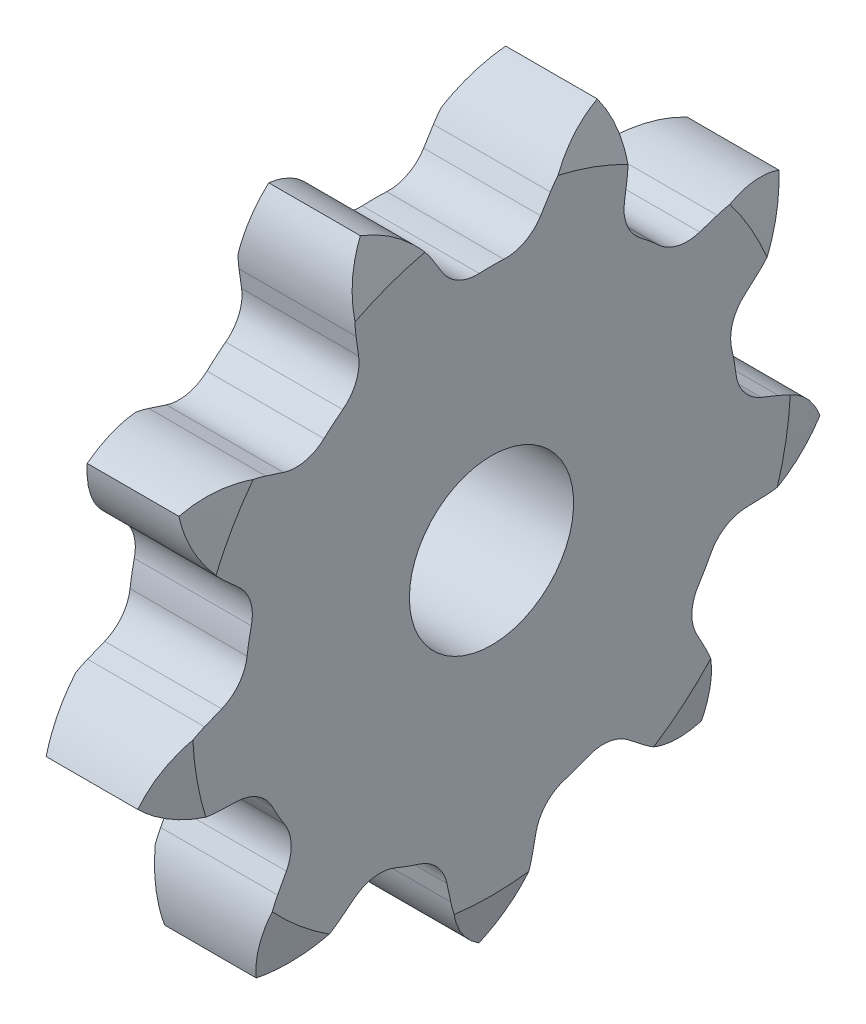
SolidWorks part; units mm, degrees
ref_plane "Plane1" through (0, 0, 0) normal (0, 0, 1) x (1, 0, 0)
ref_plane "Plane2" through (0, 0, 0) normal (0, 1, 0) x (1, 0, 0)
ref_plane "Plane3" through (0, 0, 0) normal (1, 0, 0) x (0, 0, -1)
sketch "Clipboard" plane through (0, 0, 0) normal (0, 1, 0) x (1, 0, 0)
  line L0 (0, 0) -> (62.7182, -9.9336)
  line L1 (-15, 0) -> (100, 0) construction
  line L2 (0, 0) -> (-2.1039, 2.3779)
  line L3 (0, 0) -> (-11.863, 4.5341)
  line L4 (0, 0) -> (8.5297, 1.351)
  line L5 (0, 0) -> (-71.3958, -26.6285)
  line L6 (0, 0) -> (-30.0043, -20.244)
  line L7 (-2.1039, 2.3779) -> (14.2981, 76.7917)
  line L8 (-76.2, 54.61) -> (-19.7358, 54.61)
  line L9 (-66.6514, 23.5599) -> (-51.1233, 26.8605)
  line L10 (-76.2, 71.12) -> (16.6308, 71.12)
  line L11 (0, 0) -> (-38.1, 0)
  line L12 (-76.2, 101.6) -> (-31.75, 101.6)
  circle A0 centre (0, 0) radius 15.875
  circle A1 centre (0, 0) radius 25.4
  circle A2 centre (0, 0) radius 25.4
  dimension "Num_teeth" = 9
  dimension "Pitch_radius" = 92.8308
  dimension "Width" = 38.1
  dimension "F" = 44.45
  dimension "H" = 15.875
  dimension "Thickness" = 36.195
sketch "BasProSke" plane through (0, 0, 0) normal (0, 1, 0) x (1, 0, 0)
  line L0 (-10, 0) -> (60, 0) construction
  line L1 (0, 0) -> (0, 92.496)
  line L2 (0, 0) -> (36.195, 0)
  line L3 (36.195, 0) -> (36.195, 92.496)
  line L4 (31.8516, 108.7058) -> (4.3434, 108.7058)
  line L5 (0, 92.496) -> (4.3434, 108.7058)
  line L6 (36.195, 92.496) -> (31.8516, 108.7058)
  dimension "Thickness" = 36.195
  dimension "Diameter" = 217.4116
  dimension "D1" = 15
  dimension "D2" = 15
revolve "Base-Revolve" add sketch "BasProSke" angle 360 about L0
sketch "TooCutSke" plane through (0, 0, 0) normal (1, 0, 0) x (0, 0, -1)
  line L0 (-15.1941, 82.0537) -> (-18.2226, 86.9003)
  line L1 (0, 0) -> (0, 107) construction
  line L2 (3.175, 0) -> (3.175, 119.782) construction
  line L3 (15.1941, 82.0537) -> (18.2226, 86.9003)
  line L4 (36.6386, 100.6637) -> (40.9823, 112.5978)
  line L5 (3.175, 96.303) -> (55.3039, 63.7293) construction
  line L6 (-36.6386, 100.6637) -> (-40.9823, 112.5978)
  arc A0 (3.7919, 76.0994) -> (-3.7919, 76.0994) centre (0, 0) ccw
  arc A1 (3.7919, 76.0994) -> (15.1941, 82.0537) centre (4.4239, 88.7836) ccw
  arc A2 (-3.7919, 76.0994) -> (-15.1941, 82.0537) centre (-4.4239, 88.7836) cw
  circle A3 centre (0, 0) radius 92.8308 construction
  circle A4 centre (3.175, 92.7765) radius 15.875 construction
  arc A5 (18.2226, 86.9003) -> (36.6386, 100.6637) centre (45.1481, 70.0753) cw
  arc A6 (-18.2226, 86.9003) -> (-36.6386, 100.6637) centre (-45.1481, 70.0753) ccw
  arc A7 (40.9823, 112.5978) -> (-40.9823, 112.5978) centre (0, 0) ccw
  dimension "Pitch_radius" = 92.8308
  dimension "R" = 12.7
  dimension "Dr" = 76.1938
  dimension "H" = 15.875
  dimension "Ag" = 64
  dimension "Angle" = 40
extrude "ToothCut" cut sketch "TooCutSke" along normal through all
pattern_circular "TeethCuts" count 9 every 40 about axis through (-10, 0, 0) along (1, 0, 0) of "ToothCut"
sketch "HubNeaOneSke" plane through (0, 0, 0) normal (-1, 0, 0) x (0, 0, 1)
  circle A0 centre (0, 0) radius 25.4
  dimension "Diameter" = 50.8
extrude "HubNearOne" [suppressed] add sketch "HubNeaOneSke" along normal blind 40.0051
sketch "HubNeaBotSke" plane through (0, 0, 0) normal (-1, 0, 0) x (0, 0, 1)
  circle A0 centre (0, 0) radius 25.4
  dimension "Diameter" = 50.8
extrude "HubNearBoth" [suppressed] add sketch "HubNeaBotSke" along normal blind 20.0025
ref_plane "FarPln" through (36.195, 0, 0) normal (1, 0, 0) x (0, 0, -1)
sketch "HubFarSke" plane through (36.195, 0, 0) normal (1, 0, 0) x (0, 0, -1)
  circle A0 centre (0, 0) radius 25.4
  dimension "Diameter" = 50.8
extrude "HubFar" [suppressed] add sketch "HubFarSke" along normal blind 20.0025
sketch "BorSke" plane through (0, 0, 0) normal (1, 0, 0) x (0, 0, -1)
  circle A0 centre (0, 0) radius 25.4
  dimension "Diameter" = 50.8
extrude "Bore" cut sketch "BorSke" along normal mid plane 152.4001
sketch "KeySke" plane through (0, 0, 0) normal (1, 0, 0) x (0, 0, -1)
  line L0 (-6.35, 0) -> (-6.35, 31.0642)
  line L1 (-6.35, 31.0642) -> (6.35, 31.0642)
  line L2 (6.35, 31.0642) -> (6.35, 0)
  line L3 (0, 0) -> (0, 34) construction
  line L4 (-6.35, 0) -> (6.35, 0)
  dimension "Width" = 12.7
extrude "Keyway" [suppressed] cut sketch "KeySke" along normal mid plane 152.4001
pattern_circular "Keyway2" [suppressed] count 2 every 90 about axis through (-10, 0, 0) along (1, 0, 0)
equation "\"Thickness@Clipboard\" = \"Width@Clipboard\" * 0.95"
equation "\"H@Clipboard\" = \"Diameter@Clipboard\" / 2.0"
equation "\"OAL@Clipboard\" = \"Thickness@Clipboard\""
equation "\"Pitch_radius@Clipboard\" = ( \"Pitch@Clipboard\" / 2.0) / sin(3.14159265 / \"Num_teeth@Clipboard\" )"
equation "\"MHD@Clipboard\" = (1.0 / tan(3.14159265 / \"Num_teeth@Clipboard\" ) - 0.05) * \"Pitch@Clipboard\" - \"F@Clipboard\""
equation "\"MHD@Clipboard\" = ((sgn( \"MHD@Clipboard\" - \"Hub_dia@Clipboard\" )-1)*( \"MHD@Clipboard\" - \"Hub_dia@Clipboard\" ))/-2+ \"Hub_dia@Clipboard\""
equation "\"OAL@Clipboard\" = ((sgn( \"OAL@Clipboard\" - \"Overall_len@Clipboard\" )+1)*( \"OAL@Clipboard\" - \"Overall_len@Clipboard\" ))/2 + \"Overall_len@Clipboard\" + 0.000002"
equation "\"Num_teeth@TeethCuts\" = int( \"Show_teeth@Clipboard\" ) + 1"
equation "\"Num_teeth@TeethCuts\" = ((sgn( \"Num_teeth@TeethCuts\" - \"Num_teeth@Clipboard\" )-1)*( \"Num_teeth@TeethCuts\" - \"Num_teeth@Clipboard\" ))/-2+ \"Num_teeth@Clipboard\""
equation "\"Num_teeth@TeethCuts\" = ((sgn( \"Num_teeth@TeethCuts\" - 2.0)+1)*( \"Num_teeth@TeethCuts\" - 2.0))/2 +2.0"
equation "\"Angle@TeethCuts\" = 360.0 / \"Num_teeth@Clipboard\""
equation "\"Pitch_radius@TooCutSke\" = \"Pitch_radius@Clipboard\""
equation "\"Cp@TooCutSke\" = 0.05 * \"Pitch@Clipboard\""
equation "\"Rt@TooCutSke\" = 0.5 * \"Pitch@Clipboard\""
equation "\"R@TooCutSke\"  = 0.8 * \"H@Clipboard\""
equation "\"Dr@TooCutSke\" = \"Pitch_radius@Clipboard\" - \"H@Clipboard\" - 0.03"
equation "\"Ag@TooCutSke\" =  2.0 * \"Ap@Clipboard\" + 360.0 / \"Num_teeth@Clipboard\""
equation "\"H@TooCutSke\" = \"H@Clipboard\""
equation "\"Angle@TooCutSke\" =  360.0 / \"Num_teeth@Clipboard\""
equation "\"Wf@TooCutSke\" = 0.01 * \"Pitch@Clipboard\" * \"Num_teeth@Clipboard\""
equation "\"Wf@TooCutSke\" = ((sgn( \"Wf@TooCutSke\" - \"H@Clipboard\" * 0.8 )-1)*( \"Wf@TooCutSke\" - \"H@Clipboard\" * 0.8 ))/-2+ \"H@Clipboard\" * 0.8"
equation "\"Diameter@BasProSke\" = 2.0 * \"Pitch_radius@Clipboard\"  + 2.0 * \"H@Clipboard\""
equation "\"Thickness@BasProSke\"  = \"Thickness@Clipboard\""
equation "\"G1@BasProSke\" =  \"Thickness@Clipboard\" * 0.12"
equation "\"G2@BasProSke\" =   \"Thickness@Clipboard\" * 0.12"
equation "\"Diameter@HubNeaOneSke\" = \"MHD@Clipboard\""
equation "\"Length@HubNearOne\" = \"OAL@Clipboard\" - \"Thickness@BasProSke\""
equation "\"Diameter@HubNeaBotSke\" = \"MHD@Clipboard\""
equation "\"Length@HubNearBoth\" = ( \"OAL@Clipboard\" - \"Thickness@BasProSke\" ) / 2.0"
equation "\"Thickness@FarPln\" = \"Thickness@BasProSke\""
equation "\"Diameter@HubFarSke\" = \"MHD@Clipboard\""
equation "\"Length@HubFar\" = ( \"OAL@Clipboard\" - \"Thickness@BasProSke\" ) / 2.0"
equation "\"D1@Bore\" = \"OAL@Clipboard\" * 2.0"
equation "\"D1@Keyway\" = \"OAL@Clipboard\" * 2.0"
equation "\"Offset@KeySke\" = \"T_dim@Clipboard\" - \"Diameter@BorSke\" / 2.0"
